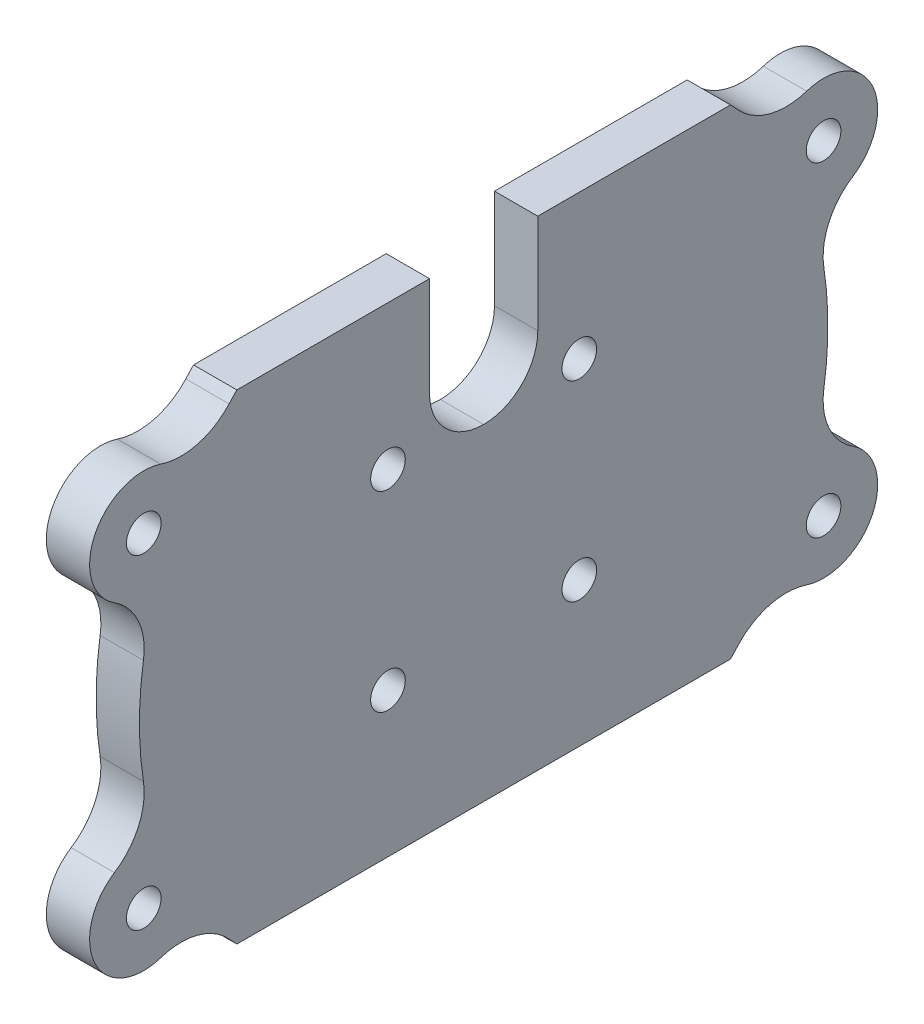
SolidWorks part; units mm, degrees
material "5052-H32"
ref_plane "Front Plane" through (0, 0, 0) normal (0, 0, 1) x (1, 0, 0)
ref_plane "Top Plane" through (0, 0, 0) normal (0, 1, 0) x (1, 0, 0)
ref_plane "Right Plane" through (0, 0, 0) normal (1, 0, 0) x (0, 0, -1)
sketch "Sketch2" plane through (0, 0, 0) normal (1, 0, 0) x (0, 0, -1)
  line L0 (5, 8) -> (5, 31.4045) construction
  line L1 (-5, 8) -> (-5, 31.4045) construction
  line L3 (5, 8) -> (-5, 8) construction
  line L5 (5, 8) -> (5, 22.1675)
  line L6 (-5, 8) -> (-5, 22.1675)
  line L8 (5, 8) -> (-5, 8)
  line L10 (-22.8, 22.1675) -> (22.8, 22.1675) construction
  line L11 (-22.8, 22.1675) -> (-5, 22.1675)
  line L12 (-22.8, -22.1675) -> (22.8, -22.1675) construction
  line L13 (-22.8, -22.1675) -> (22.8, -22.1675)
  line L14 (5, 22.1675) -> (22.8, 22.1675)
  arc A0 (23.5159, 21.4065) -> (-23.5159, 21.4065) centre (0, 0) ccw construction
  arc A1 (23.5159, 21.4065) -> (29.8338, 19.748) centre (27.9529, 25.4455) ccw construction
  arc A2 (34.1096, 10.797) -> (29.8338, 19.748) centre (31.4013, 15) ccw construction
  arc A3 (34.1096, 10.797) -> (31.4295, 4.8402) centre (37.3596, 5.7535) ccw construction
  arc A4 (31.4295, -4.8402) -> (31.4295, 4.8402) centre (0, 0) ccw construction
  arc A5 (31.4295, -4.8402) -> (34.1096, -10.797) centre (37.3596, -5.7535) ccw construction
  arc A6 (29.8338, -19.748) -> (34.1096, -10.797) centre (31.4013, -15) ccw construction
  arc A7 (29.8338, -19.748) -> (23.5159, -21.4065) centre (27.9529, -25.4455) ccw construction
  arc A8 (-23.5159, -21.4065) -> (23.5159, -21.4065) centre (0, 0) ccw construction
  arc A9 (-23.5159, -21.4065) -> (-29.8338, -19.748) centre (-27.9529, -25.4455) ccw construction
  arc A10 (-34.1096, -10.797) -> (-29.8338, -19.748) centre (-31.4013, -15) ccw construction
  arc A11 (-34.1096, -10.797) -> (-31.4295, -4.8402) centre (-37.3596, -5.7535) ccw construction
  arc A12 (-31.4295, 4.8402) -> (-31.4295, -4.8402) centre (0, 0) ccw construction
  arc A13 (-31.4295, 4.8402) -> (-34.1096, 10.797) centre (-37.3596, 5.7535) ccw construction
  arc A14 (-29.8338, 19.748) -> (-34.1096, 10.797) centre (-31.4013, 15) ccw construction
  arc A15 (-29.8338, 19.748) -> (-23.5159, 21.4065) centre (-27.9529, 25.4455) ccw construction
  arc A16 (23.5159, 21.4065) -> (22.8, 22.1675) centre (0, 0) ccw
  arc A17 (23.5159, 21.4065) -> (29.8338, 19.748) centre (27.9529, 25.4455) ccw
  arc A18 (34.1096, 10.797) -> (29.8338, 19.748) centre (31.4013, 15) ccw
  arc A19 (34.1096, 10.797) -> (31.4295, 4.8402) centre (37.3596, 5.7535) ccw
  arc A20 (31.4295, -4.8402) -> (31.4295, 4.8402) centre (0, 0) ccw
  arc A21 (31.4295, -4.8402) -> (34.1096, -10.797) centre (37.3596, -5.7535) ccw
  arc A22 (29.8338, -19.748) -> (34.1096, -10.797) centre (31.4013, -15) ccw
  arc A23 (29.8338, -19.748) -> (23.5159, -21.4065) centre (27.9529, -25.4455) ccw
  arc A24 (-23.5159, -21.4065) -> (-22.8, -22.1675) centre (0, 0) ccw
  arc A25 (-23.5159, -21.4065) -> (-29.8338, -19.748) centre (-27.9529, -25.4455) ccw
  arc A26 (-34.1096, -10.797) -> (-29.8338, -19.748) centre (-31.4013, -15) ccw
  arc A27 (-34.1096, -10.797) -> (-31.4295, -4.8402) centre (-37.3596, -5.7535) ccw
  arc A28 (-31.4295, 4.8402) -> (-31.4295, -4.8402) centre (0, 0) ccw
  arc A29 (-31.4295, 4.8402) -> (-34.1096, 10.797) centre (-37.3596, 5.7535) ccw
  arc A30 (-29.8338, 19.748) -> (-34.1096, 10.797) centre (-31.4013, 15) ccw
  arc A31 (-29.8338, 19.748) -> (-23.5159, 21.4065) centre (-27.9529, 25.4455) ccw
  arc A32 (-22.8, 22.1675) -> (-23.5159, 21.4065) centre (0, 0) ccw
  arc A33 (22.8, -22.1675) -> (23.5159, -21.4065) centre (0, 0) ccw
extrude "Boss-Extrude1" add sketch "Sketch2" along normal up to vertex from vertex
hole_wizard "CSK for M3 Countersunk Flat Head Screw1" positions "Sketch3" profile "Sketch5" countersink size "M3" standard "ISO" end condition through all
sketch "Sketch3" plane through (-50, 0, 0) normal (-1, 0, 0) x (0, 0, 1)
  point P0 (-31.4013, 15)
  point P3 (-31.4013, -15)
  point P6 (31.4013, 15)
  point P9 (31.4013, -15)
sketch "Sketch5" plane through (-50, 15, -31.4013) normal (0, 1, 0) x (0, 0, 1)
  line L0 (0, 0) -> (0, 4)
  line L1 (0, 4) -> (1.6, 4)
  line L2 (1.6, 4) -> (1.6, 1.55)
  line L3 (1.6, 1.55) -> (3.15, 0)
  line L5 (3.15, 0) -> (0, 0)
  line L6 (-1.6, 1.55) -> (-3.15, 0) construction
  line L11 (0, -6.35) -> (0, 107.95) construction
  dimension "Thru Hole Dia." = 3.2
  dimension "Thru Hole Depth" = 4
  dimension "Near C'Sink Dia." = 6.3
  dimension "Near C'Sink Angle" = 90
hole_wizard "M3 Clearance Hole1" positions "Sketch6" profile "Sketch8" hole size "M3" standard "ISO" end condition up to next
sketch "Sketch6" plane through (-50, 0, 0) normal (-1, 0, 0) x (0, 0, 1)
  point P0 (-8.8388, 8.8388)
  point P3 (-8.8388, -8.8388)
  point P6 (8.8388, -8.8388)
  point P9 (8.8388, 8.8388)
sketch "Sketch8" plane through (-50, 8.8388, -8.8388) normal (0, 1, 0) x (0, 0, 1)
  line L0 (0, 0) -> (0, 4)
  line L1 (0, 4) -> (1.6, 4)
  line L2 (1.6, 4) -> (1.6, 0)
  line L5 (1.6, 0) -> (0, 0)
  line L11 (0, -6.35) -> (0, 107.95) construction
  dimension "Thru Hole Dia." = 3.2
  dimension "Thru Hole Depth" = 4
fillet "Fillet1" radius 5 2 edges at (-48, 8, 5) (-48, 8, -5)
